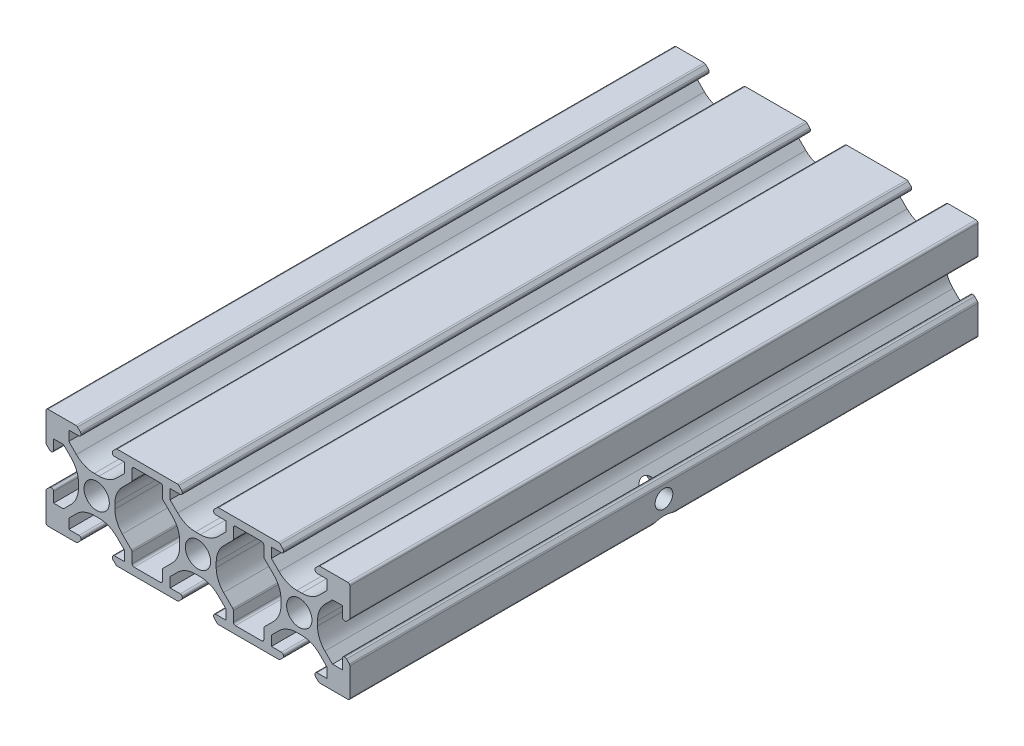
SolidWorks part; units mm, degrees
material "6063-O"
ref_plane "Plano frontal" through (0, 0, 0) normal (0, 0, 1) x (1, 0, 0)
ref_plane "Plano superior" through (0, 0, 0) normal (0, 1, 0) x (1, 0, 0)
ref_plane "Plano direito" through (0, 0, 0) normal (1, 0, 0) x (0, 0, -1)
sketch "Esboço1" plane through (0, 0, 0) normal (0, 0, 1) x (1, 0, 0)
  line L0 (-9.0343, 3.1) -> (-8.9, 3.1)
  line L3 (-10, 10) -> (-4.0657, 10)
  line L5 (-10, -10) -> (10, 10) construction
  line L6 (-10, 10) -> (10, -10) construction
  line L7 (-8.5, 3.5) -> (-8.5, 5.5)
  line L8 (-10, 0) -> (10, 0) construction
  line L9 (0, 10) -> (0, -10) construction
  line L12 (-8.5, 5.5) -> (-6.5607, 5.5)
  line L15 (-6.5607, 5.5) -> (-5.0645, 4.0038)
  line L16 (-3.6, 0.4683) -> (-3.6, 0)
  line L17 (-0.4683, 3.6) -> (0, 3.6)
  line L18 (-5.5, 6.5607) -> (-4.0038, 5.0645)
  line L21 (-5.5, 8.5) -> (-5.5, 6.5607)
  line L24 (-3.5, 8.5) -> (-5.5, 8.5)
  line L25 (-3.1, 9.0343) -> (-3.1, 8.9)
  line L44 (-10, 4.0657) -> (-10, 10)
  line L45 (-9.8828, 3.7828) -> (-9.3172, 3.2172)
  line L46 (-3.7828, 9.8828) -> (-3.2172, 9.3172)
  line L47 (-3.6, 0) -> (-2.5, 0)
  line L48 (0, 3.6) -> (0, 2.5)
  arc A0 (-3.5, 8.5) -> (-3.1, 8.9) centre (-3.5, 8.9) ccw
  arc A1 (-3.7828, 9.8828) -> (-4.0657, 10) centre (-4.0657, 9.6) ccw
  arc A2 (-10, 4.0657) -> (-9.8828, 3.7828) centre (-9.6, 4.0657) ccw
  arc A3 (-8.5, 3.5) -> (-8.9, 3.1) centre (-8.9, 3.5) cw
  arc A4 (-3.2172, 9.3172) -> (-3.1, 9.0343) centre (-3.5, 9.0343) cw
  arc A5 (-9.3172, 3.2172) -> (-9.0343, 3.1) centre (-9.0343, 3.5) ccw
  arc A6 (-3.6, 0.4683) -> (-5.0645, 4.0038) centre (-8.6, 0.4683) ccw
  arc A7 (-4.0038, 5.0645) -> (-0.4683, 3.6) centre (-0.4683, 8.6) ccw
  circle A8 centre (0, 0) radius 2.5
  point P6 (-10, 3.1)
  point P28 (-3.1, 8.5)
  point P31 (-3.1, 10)
  point P33 (-3.9, 10)
  point P36 (-10, 3.9)
  point P39 (-8.5, 3.1)
  point P42 (-3.1, 9.2)
  point P45 (-9.2, 3.1)
  point P48 (-3.6, 2.5393)
  point P51 (-2.5393, 3.6)
  dimension "D5" = 10
  dimension "D9" = 0.4
  dimension "D10" = 0.4
  dimension "D11" = 5
  dimension "D12" = 5
  dimension "D13" = 5
  dimension "D1" = 6.9
  dimension "D2" = 1.5
  dimension "D3" = 3.6
  dimension "D4" = 1.5
  dimension "D6" = 2.4
  dimension "D7" = 3.6
  dimension "D8" = 45
extrude "Ressalto-extrusão1" add sketch "Esboço1" along normal blind 124
sketch "Esboço3" plane through (0, 0, 0) normal (1, 0, 0) x (0, 0, -1)
  line L0 (0, 0) -> (-1000, 0) construction
  dimension "D1" = 1000
pattern_circular "PadrãoCircular1" count 4 over 360 about axis through (0, 0, 0) along (0, 0, 1) of "Ressalto-extrusão1"
pattern_linear "Padrão linear1" count 3 spacing 20 along (1, 0, 0) of "Ressalto-extrusão1", "PadrãoCircular1"
sketch "Esboço4" plane through (0, 0, 0) normal (0, 0, -1) x (-1, 0, 0)
  line L0 (-13.4393, 5.5) -> (-13, 5.9393)
  line L1 (-13, 8.5) -> (-13, 5.9393)
  line L2 (-10, 10) -> (-10, -10) construction
  line L3 (-4.0657, 10) -> (-15.9343, 10) construction
  line L4 (-15.9343, -10) -> (-4.0657, -10) construction
  line L5 (-11.5, 5.5) -> (-13.4393, 5.5) construction
  line L6 (-14.5, 8.5) -> (-14.5, 6.5607) construction
  line L7 (-7, 8.5) -> (-7, 5.9393)
  line L8 (-6.5607, 5.5) -> (-7, 5.9393)
  line L9 (-13, 8.5) -> (-7, 8.5)
  line L10 (-20, 0) -> (0, 0) construction
  line L11 (-13, -8.5) -> (-7, -8.5)
  line L12 (-6.5607, -5.5) -> (-7, -5.9393)
  line L13 (-7, -8.5) -> (-7, -5.9393)
  line L14 (-13, -8.5) -> (-13, -5.9393)
  line L15 (-13.4393, -5.5) -> (-13, -5.9393)
  line L16 (-13.4393, 5.5) -> (-13.4393, -5.5)
  line L17 (-6.5607, -5.5) -> (-6.5607, 5.5)
  line L31 (-40, 0) -> (-20, 0) construction
  line L32 (-33.4393, 5.5) -> (-33, 5.9393) [skipped]
  line L33 (-33, 8.5) -> (-33, 5.9393) [skipped]
  line L34 (-27, 8.5) -> (-27, 5.9393) [skipped]
  line L35 (-26.5607, 5.5) -> (-27, 5.9393) [skipped]
  line L36 (-33, 8.5) -> (-27, 8.5) [skipped]
  line L37 (-33, -8.5) -> (-27, -8.5) [skipped]
  line L38 (-26.5607, -5.5) -> (-27, -5.9393) [skipped]
  line L39 (-27, -8.5) -> (-27, -5.9393) [skipped]
  line L40 (-33, -8.5) -> (-33, -5.9393) [skipped]
  line L41 (-33.4393, -5.5) -> (-33, -5.9393) [skipped]
  line L42 (-33.4393, 5.5) -> (-33.4393, -5.5) [skipped]
  line L43 (-26.5607, -5.5) -> (-26.5607, 5.5) [skipped]
  line L44 (-30, 10) -> (-30, -10) construction
  dimension "D1" = 45
  dimension "D2" = 1.5
  dimension "D3" = 1.5
  dimension "D4" = 2
extrude "Corte-extrusão1" cut sketch "Esboço4" against normal through all
pattern_linear "Padrão linear2" count 2 spacing 20 along (1, 0, 0) of "Corte-extrusão1"
fillet "Filete1" radius 0.4 16 edges at (13, -5.9393, 62) (13, -8.5, 62) (7, -8.5, 62) (7, -5.9393, 62) (7, 8.5, 62) (7, 5.9393, 62) (13, 8.5, 62) (13, 5.9393, 62) (27, -8.5, 62) (27, -5.9393, 62) (27, 8.5, 62) (27, 5.9393, 62) (33, 8.5, 62) (33, -8.5, 62) (33, -5.9393, 62) (33, 5.9393, 62)
fillet "Filete2" radius 0.4 4 edges at (-10, 10, 62) (50, -10, 62) (50, 10, 62) (-10, -10, 62)
ref_plane "Plane1" through (0, 0, 0) normal (0, 1, 0) x (1, 0, 0)
ref_plane "Plane2" through (20, 0, 0) normal (1, 0, 0) x (0, 0, -1)
ref_plane "Plane3" through (0, 0, 62) normal (0, 0, -1) x (-1, 0, 0)
sketch "Sketch1" plane through (0, 0, 0) normal (0, 0, -1) x (-1, 0, 0)
  line L0 (-20, 0) -> (-20, -25.025) construction
  circle A0 centre (-20, -10.5) radius 5.1
  dimension "D1" = 10.2
  dimension "D2" = 10.5
sketch "Sketch2" plane through (50, 0, 0) normal (1, 0, 0) x (0, 0, -1)
  line L0 (-62, -9.6) -> (-62, 9.6) construction
  line L1 (-124, -9.6) -> (0, -9.6) construction
  line L2 (0, 9.6) -> (-124, 9.6) construction
  line L3 (-124, 10) -> (0, 10) construction
  circle A1 centre (-62, -14.5) radius 5.1
  dimension "D1" = 10.2
  dimension "D2" = 24.5
extrude "Cut-Extrude2" cut sketch "Sketch2" against normal through all
sketch "Sketch3" plane through (50, 0, 0) normal (1, 0, 0) x (0, 0, -1)
  line L0 (-62, -14.5) -> (-62, -6.5) construction
  circle A0 centre (-62, -6.5) radius 1.75
  dimension "D2" = 3.5
  dimension "D1" = 8
extrude "Cut-Extrude3" cut sketch "Sketch3" against normal through all
